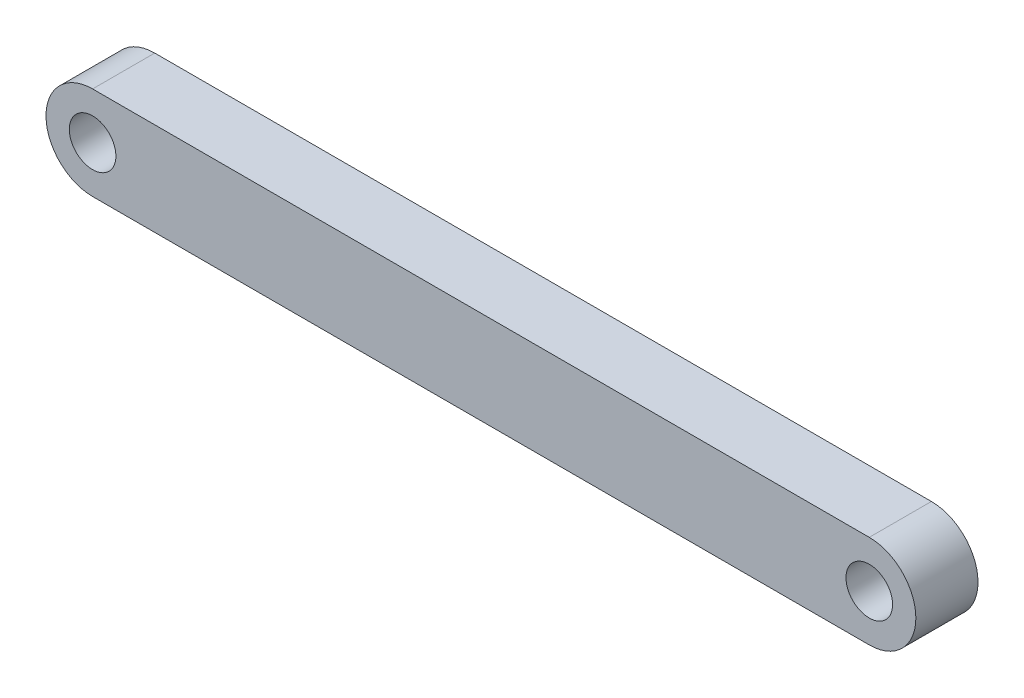
SolidWorks part; units mm, degrees
ref_plane "Front Plane" through (0, 0, 0) normal (0, 0, 1) x (1, 0, 0)
ref_plane "Top Plane" through (0, 0, 0) normal (0, 1, 0) x (1, 0, 0)
ref_plane "Right Plane" through (0, 0, 0) normal (1, 0, 0) x (0, 0, -1)
sketch "Sketch1" plane through (0, 0, 0) normal (0, 0, 1) x (1, 0, 0)
  line L0 (-25, 0) -> (25, 0) construction
  line L1 (-25, 3) -> (25, 3)
  line L2 (-25, -3) -> (25, -3)
  arc A0 (-25, 3) -> (-25, -3) centre (-25, 0) ccw
  arc A1 (25, -3) -> (25, 3) centre (25, 0) ccw
  circle A2 centre (-25, 0) radius 1.5
  circle A3 centre (25, 0) radius 1.5
  point P2 (0, 0)
  dimension "D1" = 3
  dimension "D2" = 3
  dimension "D3" = 50
extrude "Boss-Extrude1" add sketch "Sketch1" along normal blind 4
